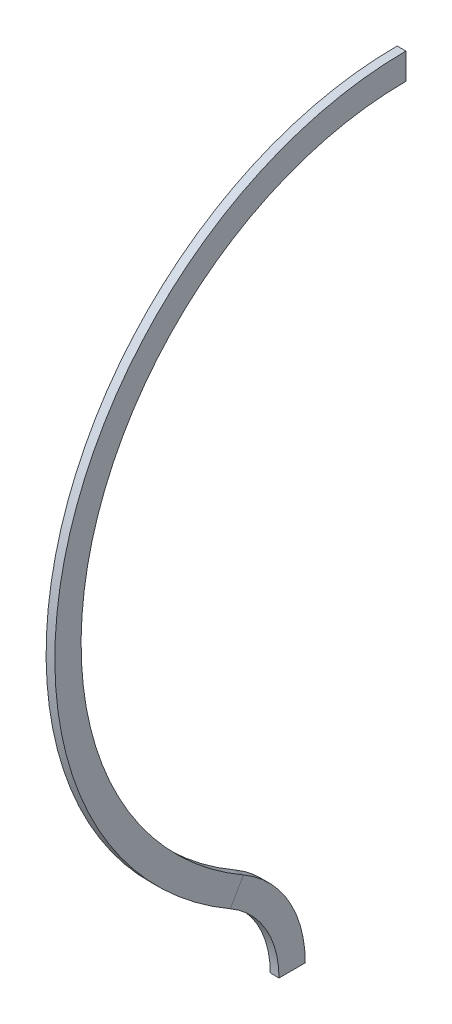
SolidWorks part; units mm, degrees
material "Thornel Mat VMA"
ref_plane "Front Plane" through (0, 0, 0) normal (0, 0, 1) x (1, 0, 0)
ref_plane "Top Plane" through (0, 0, 0) normal (0, 1, 0) x (1, 0, 0)
ref_plane "Right Plane" through (0, 0, 0) normal (1, 0, 0) x (0, 0, -1)
sketch "Sketch1" plane through (0, 0, 0) normal (1, 0, 0) x (0, 0, -1)
  line L0 (0, -19.4649) -> (0, 140) construction
  line L1 (0, 140) -> (32.3728, 140) construction
  line L2 (0, 0) -> (-23, 0) construction
  arc A0 (0, 0) -> (-25.6218, 44.3782) centre (-51.2436, 0) ccw construction
  arc A1 (-25.6218, 44.3782) -> (0, 140) centre (0, 88.7564) cw construction
  arc A2 (0, 163) -> (-37.1218, 24.4596) centre (0, 88.7564) ccw
  arc A3 (-37.1218, 24.4596) -> (-23, 0) centre (-51.2436, 0) cw
  dimension "D2" = 23
  dimension "D3" = 23
  dimension "D1" = 140
sketch "Sketch2" plane through (0, 0, 0) normal (0, 1, 0) x (1, 0, 0)
  line L0 (0, 0) -> (0, -23) construction
  line L1 (0, -23) -> (2, -23)
  line L2 (0, -23) -> (0, -29)
  line L3 (0, -29) -> (2, -29)
  line L4 (2, -23) -> (2, -29)
  dimension "D1" = 2
  dimension "D2" = 6
sweep "Sweep1" add profiles "Sketch2" path "Sketch1"
